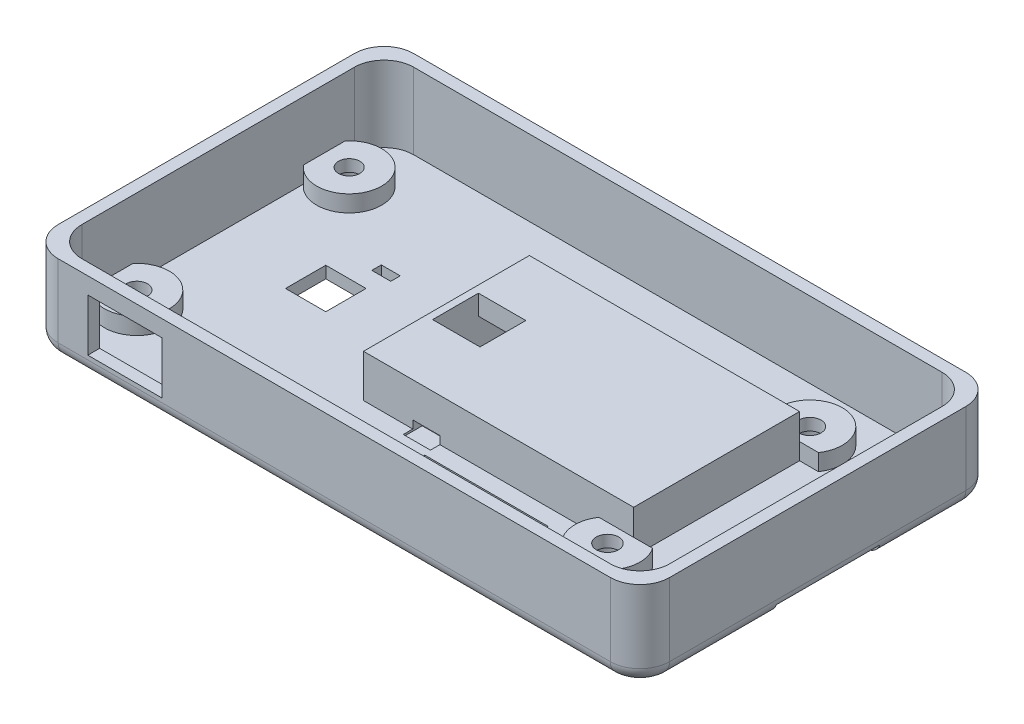
SolidWorks part; units mm, degrees
material "ABS"
ref_plane "Спереди" through (0, 0, 0) normal (0, 0, 1) x (1, 0, 0)
ref_plane "Сверху" through (0, 0, 0) normal (0, 1, 0) x (1, 0, 0)
ref_plane "Справа" through (0, 0, 0) normal (1, 0, 0) x (0, 0, -1)
sketch "Эскиз1" plane through (0, 0, 0) normal (0, 1, 0) x (1, 0, 0)
  line L11 (61.92, -36) -> (-61.92, -36)
  line L12 (61.92, -36) -> (61.92, 36)
  line L13 (61.92, 36) -> (-61.92, 36)
  line L14 (-61.92, -36) -> (-61.92, 36)
  point P0 (0, 0)
extrude "Бобышка-Вытянуть1" add sketch "Эскиз1" along normal blind 17.76
sketch "Эскиз8" plane through (0, 17.76, 0) normal (0, 1, 0) x (1, 0, 0)
  line L7 (-59.52, 33.6) -> (59.52, 33.6)
  line L8 (-59.52, 33.6) -> (-59.52, -33.6)
  line L9 (-59.52, -33.6) -> (59.52, -33.6)
  line L10 (59.52, 33.6) -> (59.52, -33.6)
extrude "Вырез-Вытянуть5" cut sketch "Эскиз8" against normal blind 15.36
sketch "Эскиз10" plane through (0, 2.4, 0) normal (0, 1, 0) x (1, 0, 0)
  line L2 (39.24, -14.6) -> (-15.48, -14.6)
  line L6 (-15.48, -14.6) -> (-15.48, 19)
  line L7 (39.24, 19) -> (-15.48, 19)
  line L8 (39.24, -14.6) -> (39.24, 19)
sketch "Эскиз11" plane through (0, 0, 33.6) normal (0, 0, 1) x (1, 0, 0)
  line L3 (-49.92, 3.84) -> (-34.92, 3.84)
  line L4 (-49.92, 3.84) -> (-49.92, 14.4)
  line L5 (-49.92, 14.4) -> (-34.92, 14.4)
  line L6 (-34.92, 3.84) -> (-34.92, 14.4)
extrude "Бобышка-Вытянуть2" add sketch "Эскиз10" along normal blind 8.64
extrude "Вырез-Вытянуть7" cut sketch "Эскиз11" along normal blind 5
sketch "Эскиз12" plane through (0, 0, 0) normal (0, -1, 0) x (1, 0, 0)
  line L5 (-14.04, 12.68) -> (37.32, 12.68)
  line L6 (-14.04, 12.68) -> (-14.04, -17.56)
  line L7 (-14.04, -17.56) -> (37.32, -17.56)
  line L8 (37.32, 12.68) -> (37.32, -17.56)
  point P3 (57.4685, 0)
extrude "Вырез-Вытянуть8" cut sketch "Эскиз12" against normal blind 7
sketch "Эскиз13" plane through (0, 0, 0) normal (0, -1, 0) x (1, 0, 0)
  line L0 (61.92, 36) -> (61.92, -36) construction
  line L2 (61.92, 8.2) -> (37.32, 8.2)
  line L3 (37.32, -17.56) -> (37.32, 12.68) construction
  line L4 (61.92, 8.2) -> (61.92, -12.76)
  line L5 (37.32, 8.2) -> (37.32, -12.76)
  line L6 (37.32, -12.76) -> (61.92, -12.76)
  point P12 (0, 0)
extrude "Вырез-Вытянуть9" cut sketch "Эскиз13" against normal blind 2
sketch "Эскиз21" plane through (0, 7, 0) normal (0, -1, 0) x (1, 0, 0)
  line L0 (-14.04, 12.68) -> (-14.04, -17.56) construction
  line L1 (0, 0) -> (48.3033, 0) construction
  line L2 (-14.04, -2.44) -> (-14.04, 2.04)
  line L3 (-14.04, -2.44) -> (-14.04, -7.24)
  line L4 (-14.04, 2.04) -> (-4.44, 2.04)
  line L5 (-14.04, -7.24) -> (-4.44, -7.24)
  line L6 (-4.44, -7.24) -> (-4.44, 2.04)
extrude "Вырез-Вытянуть16" cut sketch "Эскиз21" against normal through all
sketch "Эскиз14" plane through (0, 0, 0) normal (0, -1, 0) x (1, 0, 0)
  circle A0 centre (37.64, -22.7) radius 2.26
  circle A1 centre (-54.48, -21.5) radius 2.16
  circle A2 centre (37.64, 18.3) radius 2.26
  circle A6 centre (-54.48, 21.5) radius 2.16
  point P4 (0, 0)
sketch "Эскиз22" plane through (0, 0, 0) normal (0, -1, 0) x (1, 0, 0)
  circle A4 centre (-54.48, 21.5) radius 3.12
  circle A5 centre (-54.48, -21.5) radius 3.12
  circle A6 centre (37.64, -22.7) radius 3.71
  circle A7 centre (37.64, 18.3) radius 3.71
fillet "Скругление1" radius 6 4 edges at (-61.92, 8.88, 36) (-61.92, 8.88, -36) (61.92, 8.88, -36) (61.92, 8.88, 36)
fillet "Скругление3" radius 3 8 edges at (60.1626, 0, -34.2426) (0, 0, -36) (-60.1626, 0, -34.2426) (-61.92, 0, 0) (-60.1626, 0, 34.2426) (61.92, 0, 19.1) (60.1626, 0, 34.2426) (0, 0, 36)
fillet "Скругление5" radius 6 4 edges at (-59.52, 10.08, 33.6) (-59.52, 10.08, -33.6) (59.52, 10.08, 33.6) (59.52, 10.08, -33.6) tangent propagation no
sketch "Эскиз19" plane through (0, 0, 12.68) normal (0, 0, -1) x (-1, 0, 0)
  line L4 (5.5, 2) -> (0, 2)
  line L5 (5.5, 2) -> (5.5, 4)
  line L6 (5.5, 4) -> (0, 4)
  line L7 (0, 2) -> (0, 4)
extrude "Вырез-Вытянуть14" cut sketch "Эскиз19" against normal blind 3.84
sketch "Эскиз20" plane through (0, 0, -17.56) normal (0, 0, 1) x (1, 0, 0)
  line L4 (-5.5, 2) -> (0, 2)
  line L5 (-5.5, 2) -> (-5.5, 4)
  line L6 (-5.5, 4) -> (0, 4)
  line L7 (0, 2) -> (0, 4)
extrude "Вырез-Вытянуть15" cut sketch "Эскиз20" against normal blind 3.84
sketch "Эскиз23" plane through (0, 2.4, 0) normal (0, 1, 0) x (1, 0, 0)
  line L1 (-59.52, 25.7302) -> (-59.52, 17.2698)
  line L3 (-59.52, 27.6) -> (-59.52, -27.6) construction
  line L4 (-59.52, -25.7302) -> (-59.52, -17.2698)
  arc A0 (-59.52, 17.2698) -> (-59.52, 25.7302) centre (-54.48, 21.5) ccw
  arc A2 (-59.52, -25.7302) -> (-59.52, -17.2698) centre (-54.48, -21.5) ccw
sketch "Эскиз24" plane through (0, 2.4, 0) normal (0, 1, 0) x (1, 0, 0)
  line L0 (39.24, 19) -> (-15.48, 19) construction
  line L1 (32.1988, -14.6) -> (43.0759, -14.5923)
  line L2 (32.1988, 19) -> (43.0812, 19)
  line L4 (-15.48, -14.6) -> (39.24, -14.6) construction
  arc A0 (32.1988, -14.6) -> (43.0759, -14.5923) centre (37.64, -18.3) ccw
  arc A1 (32.1988, 19) -> (43.0812, 19) centre (37.64, 22.7) cw
extrude "Бобышка-Вытянуть3" add sketch "Эскиз24" along normal blind 3.36
extrude "Бобышка-Вытянуть4" add sketch "Эскиз23" along normal blind 3.36
sketch "Эскиз25" plane through (0, 0, 0) normal (0, 1, 0) x (1, 0, 0)
  circle A0 centre (-54.48, -21.5) radius 2.16
  circle A1 centre (-54.48, 21.5) radius 2.16
  circle A2 centre (37.64, 22.7) radius 2.26
  circle A3 centre (37.64, -18.3) radius 2.26
extrude "Вырез-Вытянуть17" cut sketch "Эскиз25" along normal through all
extrude "Вырез-Вытянуть18" cut sketch "Эскиз22" against normal blind 3.36
sketch "Эскиз26" plane through (0, 0, 0) normal (0, -1, 0) x (1, 0, 0)
  line L3 (25.2416, 17.96) -> (0.2816, 17.96)
  line L4 (25.2416, 17.96) -> (25.2416, 29)
  line L5 (25.2416, 29) -> (0.2816, 29)
  line L6 (0.2816, 17.96) -> (0.2816, 29)
  line L8 (-33.64, -11) -> (-37.48, -11)
  line L9 (-34.88, 2.84) -> (-43.04, 2.84)
  line L10 (-34.88, 2.84) -> (-34.88, -5.32)
  line L11 (-34.88, -5.32) -> (-43.04, -5.32)
  line L12 (-43.04, 2.84) -> (-43.04, -5.32)
  line L13 (-37.48, -11) -> (-37.48, -9.08)
  line L14 (-37.48, -9.08) -> (-33.64, -9.08)
  line L15 (-33.64, -9.08) -> (-33.64, -11)
extrude "Вырез-Вытянуть19" cut sketch "Эскиз26" against normal through all
